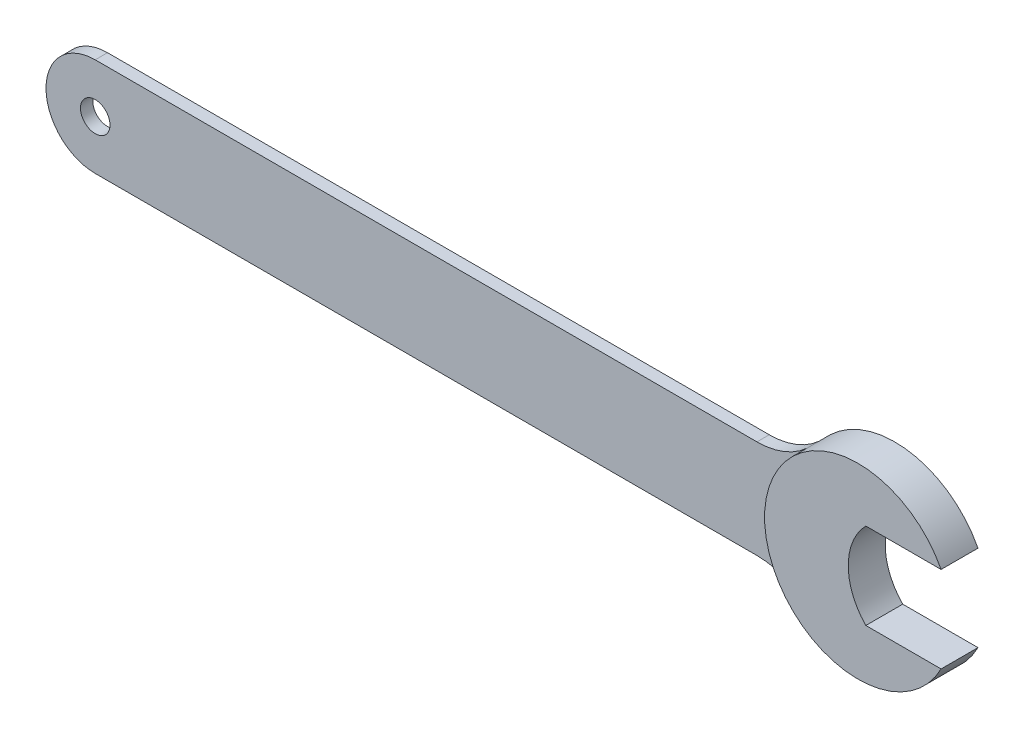
SolidWorks part; units mm, degrees
ref_plane "Front Plane" through (0, 0, 0) normal (0, 0, 1) x (1, 0, 0)
ref_plane "Top Plane" through (0, 0, 0) normal (0, 1, 0) x (1, 0, 0)
ref_plane "Right Plane" through (0, 0, 0) normal (1, 0, 0) x (0, 0, -1)
sketch "Sketch1" plane through (0, 0, 0) normal (0, 0, 1) x (1, 0, 0)
  line L0 (0, 20) -> (268.9131, 20)
  line L1 (0, -20) -> (268.9131, -20)
  line L2 (0, 0) -> (315, 0) construction
  line L3 (348.7305, 17.5) -> (318.1464, 17.5)
  line L4 (348.7305, -17.5) -> (318.1464, -17.5)
  line L5 (348.7305, 17.5) -> (318.1464, 17.5)
  circle A0 centre (0, 0) radius 6
  circle A1 centre (0, 0) radius 20
  arc A3 (289.2456, -27.9412) -> (348.7305, -17.5) centre (315, 0) ccw
  arc A4 (318.1464, 17.5) -> (311, 0) centre (336, 0) ccw
  arc A5 (318.1464, -17.5) -> (318.1464, 17.5) centre (336, 0) cw
  arc A6 (289.2456, -27.9412) -> (268.9131, -20) centre (268.9131, -50) ccw
  arc A7 (289.2456, 27.9412) -> (268.9131, 20) centre (268.9131, 50) cw
  arc A8 (289.2456, 27.9412) -> (348.7305, 17.5) centre (315, 0) cw
  circle A9 centre (315, 0) radius 38 construction
  arc A10 (289.2456, 27.9412) -> (289.2456, -27.9412) centre (315, 0) ccw
  point P20 (277, 0)
  dimension "D1" = 12
  dimension "D2" = 40
  dimension "D3" = 38
  dimension "D4" = 25
  dimension "D8" = 30
  dimension "D6" = 34
  dimension "D5" = 35
  dimension "D7" = 315
extrude "Boss-Extrude1" add sketch "Sketch1" along normal mid plane 5 contours A10 A7 L0 A1 L1 A6 | A1 A0 region at (147.7999, 0, 0) region at (13.7421, 13.7421, 0)
extrude "Boss-Extrude2" add sketch "Sketch1<4>" along normal mid plane 15 contours A8 A10 A3 L4 A5 A4 L3 region at (307.6862, 0, 0)
sketch "Sketch1<4>" plane through (0, 0, 0) normal (0, 0, 1) x (1, 0, 0) same geometry as "Sketch1"
